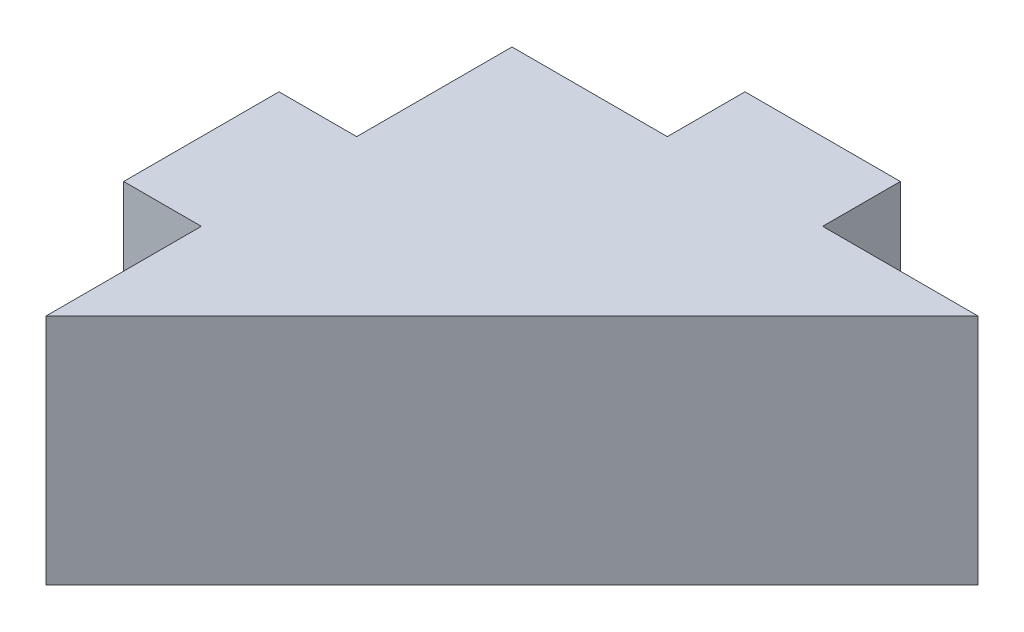
SolidWorks part; units mm, degrees
ref_plane "Plan de face" through (0, 0, 0) normal (0, 0, 1) x (1, 0, 0)
ref_plane "Plan de dessus" through (0, 0, 0) normal (0, 1, 0) x (1, 0, 0)
ref_plane "Plan de droite" through (0, 0, 0) normal (1, 0, 0) x (0, 0, -1)
sketch "Esquisse1" plane through (0, 0, 0) normal (0, 1, 0) x (1, 0, 0)
  line L1 (0, 0) -> (30, 0)
  line L2 (0, 0) -> (0, -30)
  line L3 (0, -30) -> (30, -30)
  line L4 (30, 0) -> (30, -30)
  dimension "D1" = 30
  dimension "D2" = 30
extrude "Boss.-Extru.1" add sketch "Esquisse1" along normal blind 15
ref_plane "Plan1" through (0, 0, 0) normal (0.7071, 0, -0.7071) x (-0.7071, 0, -0.7071)
sketch "Esquisse3" plane through (0, 0, 0) normal (0, 0, -1) x (-1, 0, 0)
  line L0 (-30, 15) -> (0, 15) construction
  line L1 (-20, 15) -> (-10, 15)
  line L2 (-20, 15) -> (-20, 0)
  line L3 (-20, 0) -> (-10, 0)
  line L4 (-10, 15) -> (-10, 0)
  line L5 (-30, 0) -> (0, 0) construction
  line L6 (-30, 15) -> (-30, 0) construction
  dimension "D1" = 10
  dimension "D2" = 10
extrude "Boss.-Extru.2" add sketch "Esquisse3" along normal blind 5
mirror "Symétrie1" about plane through (0, 0, 0) normal (0.7071, 0, -0.7071) of "Boss.-Extru.2"
chamfer "Chanfrein1" distance 30 angle 45 1 edges at (30, 7.5, 30)
